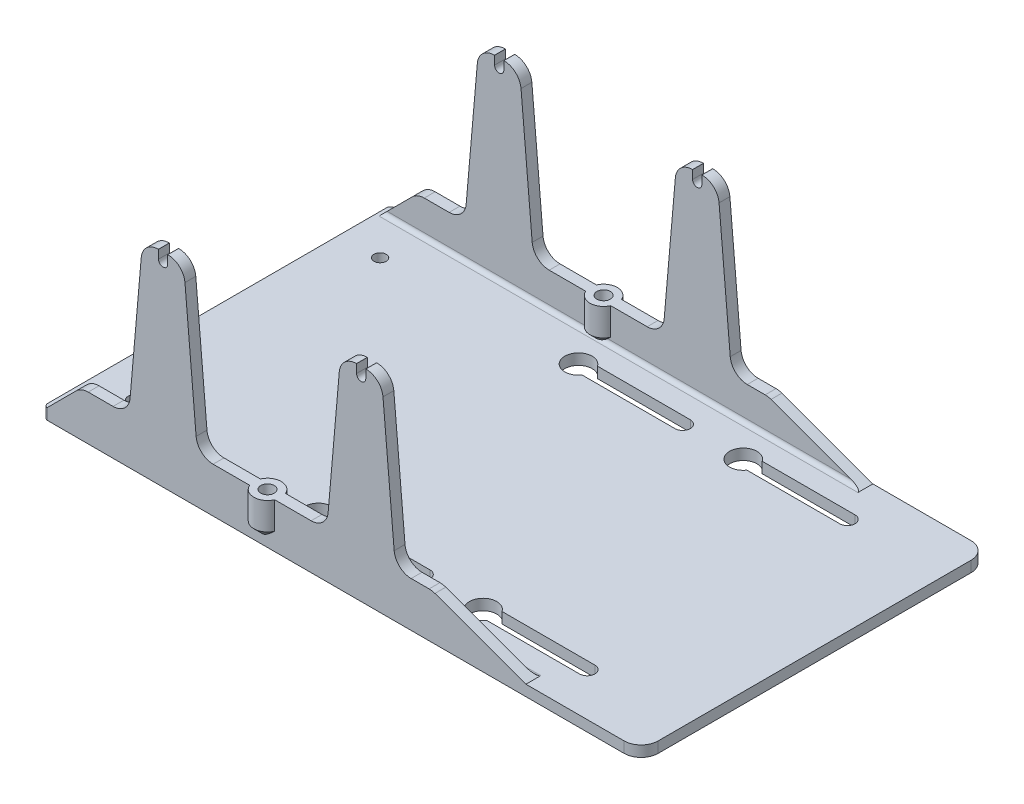
SolidWorks part; units mm, degrees
ref_plane "Front Plane" through (0, 0, 0) normal (0, 0, 1) x (1, 0, 0)
ref_plane "Top Plane" through (0, 0, 0) normal (0, 1, 0) x (1, 0, 0)
ref_plane "Right Plane" through (0, 0, 0) normal (1, 0, 0) x (0, 0, -1)
sketch "Sketch1" plane through (0, 0, 0) normal (0, 1, 0) x (1, 0, 0)
  line L0 (0, 0) -> (175, 0) construction
  line L1 (0, 50.8) -> (175, 50.8)
  line L2 (0, 50.8) -> (0, -50.8)
  line L3 (0, -50.8) -> (175, -50.8)
  line L4 (175, 50.8) -> (175, -50.8)
  line L5 (0, 50.8) -> (175, -50.8) construction
  line L6 (0, -50.8) -> (175, 50.8) construction
  point P0 (11.3289, 32.4526)
  point P5 (0, 0)
  dimension "D1" = 101.6
  dimension "D2" = 175
extrude "plate" add sketch "Sketch1" along normal blind 3.175
sketch "Sketch14" plane through (0, 0, 0) normal (0, -1, 0) x (1, 0, 0)
  text T0 "BOTTOM" font "Century Gothic" height 3.5
extrude "bottom label" cut sketch "Sketch14" against normal blind 0.6
hole_wizard "mount slots" positions "Sketch8" profile "Sketch9" size "M4" standard "ISO" slot yes end condition through all
sketch "Sketch8" plane through (0, 3.175, 0) normal (0, 1, 0) x (1, 0, 0)
  line L0 (83, 38.1) -> (131.26, 38.1) construction
  line L2 (0, 0) -> (175, 0) construction
  line L3 (175, -50.8) -> (175, 50.8) construction
  line L4 (0, 50.8) -> (0, -50.8) construction
  line L5 (83, -38.1) -> (131.26, -38.1) construction
  line L6 (65.5, 38.1) -> (100.5, 38.1) construction
  point P1 (83, 38.1)
  point P2 (131.26, 38.1)
  point P23 (131.26, -38.1)
  point P24 (83, -38.1)
  dimension "D1" = 48.26
  dimension "D2" = 38.1
  dimension "D3" = 83
  dimension "D4" = 35
sketch "Sketch9" plane through (83, 3.175, -38.1) normal (1, 0, 0) x (0, 0, 1)
  line L0 (0, 0) -> (0, 3.175)
  line L1 (0, 3.175) -> (2.25, 3.175)
  line L2 (2.25, 3.175) -> (2.25, 0)
  line L5 (2.25, 0) -> (0, 0)
  line L11 (0, -6.35) -> (0, 107.95) construction
  dimension "Thru Hole Dia." = 4.5
  dimension "Thru Hole Depth" = 3.175
sketch "Sketch12" plane through (0, 3.175, 0) normal (0, 1, 0) x (1, 0, 0)
  line L0 (-1.7462, 0) -> (1.7462, 0) construction
  circle A0 centre (116.01, 38.1) radius 4
  circle A1 centre (67.75, 38.1) radius 4
  circle A5 centre (67.75, -38.1) radius 4
  circle A6 centre (116.01, -38.1) radius 4
  arc A7 (67.75, 40.35) -> (67.75, 35.85) centre (67.75, 38.1) ccw construction
  arc A8 (116.01, 40.35) -> (116.01, 35.85) centre (116.01, 38.1) ccw construction
  dimension "D1" = 8
  dimension "D2" = 8
extrude "slot_clearance" cut sketch "Sketch12" against normal through all
hole_wizard "bracket  holes" positions "Sketch10" profile "Sketch11" hole size "M3" standard "ISO" end condition through all
sketch "Sketch10" plane through (0, 3.175, 0) normal (0, 1, 0) x (1, 0, 0)
  line L0 (0, 0) -> (175, 0) construction
  line L1 (0, 50.8) -> (0, -50.8) construction
  line L2 (175, -50.8) -> (175, 50.8) construction
  point P0 (11.75, 36)
  point P14 (11.75, -36)
  dimension "D1" = 11.75
  dimension "D2" = 36
sketch "Sketch11" plane through (11.75, 3.175, -36) normal (1, 0, 0) x (0, 0, 1)
  line L0 (0, 0) -> (0, 3.175)
  line L1 (0, 3.175) -> (1.8, 3.175)
  line L2 (1.8, 3.175) -> (1.8, 0)
  line L5 (1.8, 0) -> (0, 0)
  line L11 (0, -6.35) -> (0, 107.95) construction
  dimension "Thru Hole Dia." = 3.6
  dimension "Thru Hole Depth" = 3.175
sketch "Sketch13" plane through (0, 0, -50.8) normal (0, 0, -1) x (-1, 0, 0)
  line L0 (-141.26, 3.175) -> (-113.7852, 13.175)
  line L1 (-175, 3.175) -> (0, 3.175) construction
  line L2 (-113.7852, 13.175) -> (-11, 13.175)
  line L3 (-11, 13.175) -> (-1, 3.175)
  line L4 (-1, 3.175) -> (-141.26, 3.175)
  line L6 (0, 3.175) -> (0, 0) construction
  point P10 (0, 1.5875)
  dimension "D1" = 20
  dimension "D2" = 10
  dimension "D3" = 45
  dimension "D4" = 1
  dimension "D5" = 10
extrude "plate stiffener" add sketch "Sketch13" against normal blind 3.175
sketch "Sketch15" plane through (0, 0, -50.8) normal (0, 0, -1) x (-1, 0, 0)
  line L0 (-45.0682, 13.175) -> (-41, 59.675)
  line L1 (-11, 13.175) -> (-113.7852, 13.175) construction
  line L2 (-41, 59.675) -> (-29, 59.675) construction
  line L3 (-29, 59.675) -> (-24.9318, 13.175)
  line L4 (-35, 59.675) -> (-35, 13.175) construction
  line L5 (0, 3.175) -> (0, 0) construction
  line L6 (-45.0682, 13.175) -> (-24.9318, 13.175) construction
  line L7 (-36.35, 59.675) -> (-36.35, 57.175)
  line L8 (-33.65, 59.675) -> (-33.65, 57.175)
  line L9 (0, 3.175) -> (-175, 3.175) construction
  line L10 (-36.35, 59.675) -> (-41, 59.675)
  line L11 (-33.65, 59.675) -> (-29, 59.675)
  line L12 (-45.0682, 13.175) -> (-24.9318, 13.175)
  arc A0 (-36.35, 57.175) -> (-33.65, 57.175) centre (-35, 57.175) ccw
  point P10 (-35, 13.175)
  dimension "D3" = 2.7
  dimension "D1" = 35
  dimension "D2" = 12
  dimension "D4" = 54
  dimension "D5" = 2.5
  dimension "D6" = 85
extrude "rack ears" add sketch "Sketch15" against normal blind 3.175
sketch "Sketch16" plane through (0, 59.675, 0) normal (0, 1, 0) x (1, 0, 0)
  line L0 (41, 47.625) -> (29, 50.8) construction
  line L1 (41, 50.8) -> (29, 47.625) construction
  point P8 (35, 49.2125)
ref_axis "Axis1" through (35, 59.675, -49.2125) along (0, 1, 0)
pattern_linear "LPattern1" count 2 spacing 58 along (1, 0, 0) of "rack ears"
sketch "Sketch17" plane through (0, 3.175, 0) normal (0, 1, 0) x (1, 0, 0)
  line L0 (45.0682, 49.2125) -> (82.9318, 49.2125) construction
  line L1 (45.0682, 47.625) -> (45.0682, 50.8) construction
  line L2 (82.9318, 47.625) -> (82.9318, 50.8) construction
  point P9 (64, 49.2125)
ref_axis "Axis3" through (64, 3.175, -49.2125) along (0, 1, 0)
ref_plane "Plane1" through (0, 0, -49.2125) normal (0, 0, -1) x (-1, 0, 0)
sketch "Sketch21" plane through (0, 0, -49.2125) normal (0, 0, -1) x (-1, 0, 0)
  line L0 (-64, 1.175) -> (-60, 5.175)
  line L1 (-60, 5.175) -> (-60, 13.175)
  line L3 (-64, 13.175) -> (-64, 1.175)
  line L4 (-64, 13.175) -> (-60, 13.175)
  line L5 (-45.0682, 13.175) -> (-82.9318, 13.175) construction
  line L8 (-64, 3.175) -> (-64, 69.9522) construction
  dimension "D1" = 45
  dimension "D2" = 8
  dimension "D3" = 4
revolve "clamp boss" add sketch "Sketch21" angle 360 about axis through (64, 3.175, -49.2125) along (0, 1, 0)
hole_wizard "Tap Drill for M2.5 Tap1" positions "Sketch18" profile "Sketch19" hole size "M2.5" standard "ISO"
sketch "Sketch18" plane through (0, 13.175, 0) normal (0, 1, 0) x (1, 0, 0)
  point P0 (64, 49.2125)
sketch "Sketch19" plane through (64, 13.175, -49.2125) normal (1, 0, 0) x (0, 0, 1)
  line L0 (0, 0) -> (0, 9.0635)
  line L1 (0, 9.0635) -> (1.77, 8)
  line L2 (1.77, 8) -> (1.77, 2.8601)
  line L3 (1.77, 2.8601) -> (1.97, 0)
  line L5 (1.97, 0) -> (0, 0)
  line L6 (-1.77, 2.8601) -> (-1.97, 0) construction
  line L10 (0, 9.0635) -> (-1.77, 8) construction
  line L11 (0, -6.35) -> (0, 107.95) construction
  dimension "Hole Dia." = 3.54
  dimension "Hole Depth" = 8
  dimension "Near C'Sink Dia." = 3.94
  dimension "Near C'Sink Angle" = 8
  dimension "Drill Angle" = 118
mirror "stiffener mirror" about plane through (0, 0, 0) normal (0, 0, 1) of "clamp boss", "LPattern1", "plate stiffener", "Tap Drill for M2.5 Tap1"
fillet "Fillet3" radius 5 20 edges at (29, 59.675, -49.2125) (41, 59.675, -49.2125) (87, 59.675, -49.2125) (99, 59.675, -49.2125) (24.9318, 13.175, -49.2125) (45.0682, 13.175, -49.2125) (82.9318, 13.175, -49.2125) (103.0682, 13.175, -49.2125) (87, 59.675, 49.2125) (99, 59.675, 49.2125) (11, 13.175, -49.2125) (113.7852, 13.175, -49.2125) (113.7852, 13.175, 49.2125) (103.0682, 13.175, 49.2125) (82.9318, 13.175, 49.2125) (45.0682, 13.175, 49.2125) (11, 13.175, 49.2125) (24.9318, 13.175, 49.2125) (41, 59.675, 49.2125) (29, 59.675, 49.2125)
fillet "Fillet 1.2mm" radius 1.2 6 edges at (103.2382, 3.175, 47.625) (31.8918, 3.175, 47.625) (103.2382, 3.175, -47.625) (31.8918, 3.175, -47.625) (0, 1.5875, -50.8) (0, 1.5875, 50.8)
fillet "Fillet2" radius 5 2 edges at (175, 1.5875, 50.8) (175, 1.5875, -50.8)
